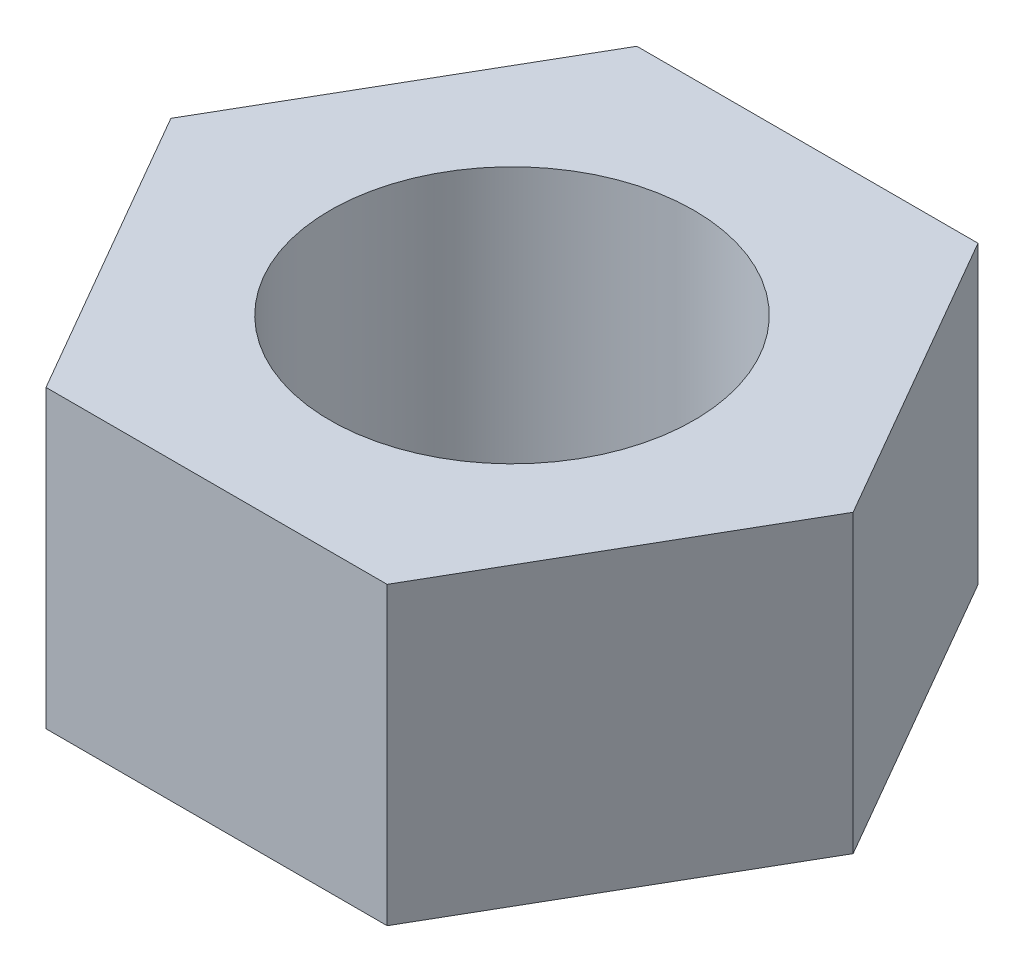
SolidWorks part; units mm, degrees
material "Plain Carbon Steel"
ref_plane "Front Plane" through (0, 0, 0) normal (0, 0, 1) x (1, 0, 0)
ref_plane "Top Plane" through (0, 0, 0) normal (0, 1, 0) x (1, 0, 0)
ref_plane "Right Plane" through (0, 0, 0) normal (1, 0, 0) x (0, 0, -1)
sketch "Sketch1" plane through (0, 0, 0) normal (0, 1, 0) x (1, 0, 0)
  line L1 (3.75, -6.4952) -> (7.5, 0)
  line L2 (7.5, 0) -> (3.75, 6.4952)
  line L3 (3.75, 6.4952) -> (-3.75, 6.4952)
  line L4 (-3.75, 6.4952) -> (-7.5, 0)
  line L5 (-7.5, 0) -> (-3.75, -6.4952)
  line L6 (-3.75, -6.4952) -> (3.75, -6.4952)
  circle A0 centre (0, 0) radius 6.4952 construction
  circle A1 centre (0, 0) radius 4
  dimension "D2" = 8
  dimension "D1" = 15
extrude "Boss-Extrude1" add sketch "Sketch1" along normal blind 6.5
